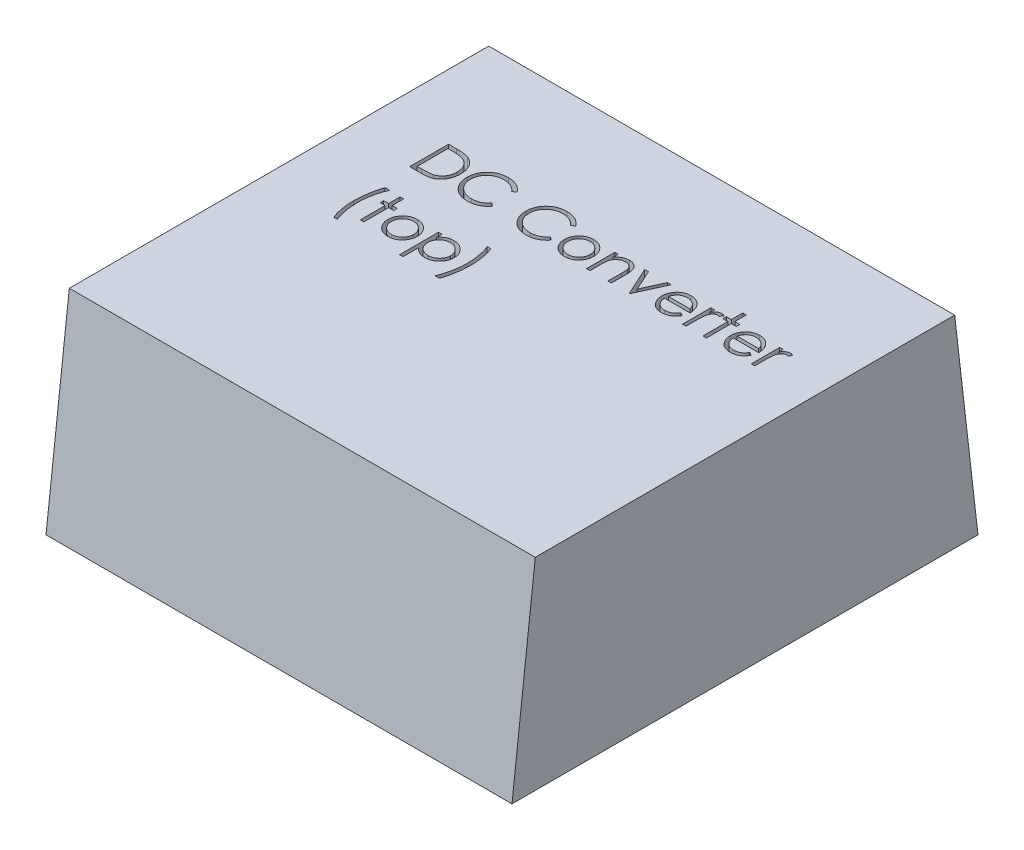
SolidWorks part; units mm, degrees
ref_plane "Front Plane" through (0, 0, 0) normal (0, 0, 1) x (1, 0, 0)
ref_plane "Top Plane" through (0, 0, 0) normal (0, 1, 0) x (1, 0, 0)
ref_plane "Right Plane" through (0, 0, 0) normal (1, 0, 0) x (0, 0, -1)
sketch "Sketch1" plane through (0, 0, 0) normal (1, 0, 0) x (0, 0, -1)
  line L0 (-125.5336, 0) -> (141.543, 0) construction
  line L1 (0, 87.035) -> (0, -86.5267) construction
  line L2 (38.1, 0) -> (-38.1, 0)
  line L3 (38.1, 0) -> (34.29, 33.02)
  line L4 (-34.29, 33.02) -> (34.29, 33.02)
  line L5 (-38.1, 0) -> (-34.29, 33.02)
  point P8 (0, 0)
  point P11 (0, 33.02)
extrude "Boss-Extrude1" add sketch "Sketch1" along normal blind 38.1 and the other way blind 38.1
sketch "Sketch2" plane through (0, 33.02, 0) normal (0, 1, 0) x (1, 0, 0)
  text T0 "DC Converter\r\n(top)" font "Century Gothic" height 6.35
extrude "Cut-Extrude1" cut sketch "Sketch2" against normal blind 7.62
sketch "Sketch3" plane through (-38.1, 0, 0) normal (-1, 0, 0) x (0, 0, 1)
  line L0 (0, 61.5461) -> (0, -18.0335) construction
  line L1 (25.4, 0) -> (-25.4, 0)
  line L2 (38.1, 0) -> (-38.1, 0) construction
  line L3 (-25.4, 0) -> (-25.4, 17.78)
  line L4 (-25.4, 17.78) -> (25.4, 17.78)
  line L5 (25.4, 0) -> (25.4, 17.78)
  point P10 (0, 17.78)
  point P11 (0, 0)
extrude "Boss-Extrude2" add sketch "Sketch3" along normal blind 6.35
